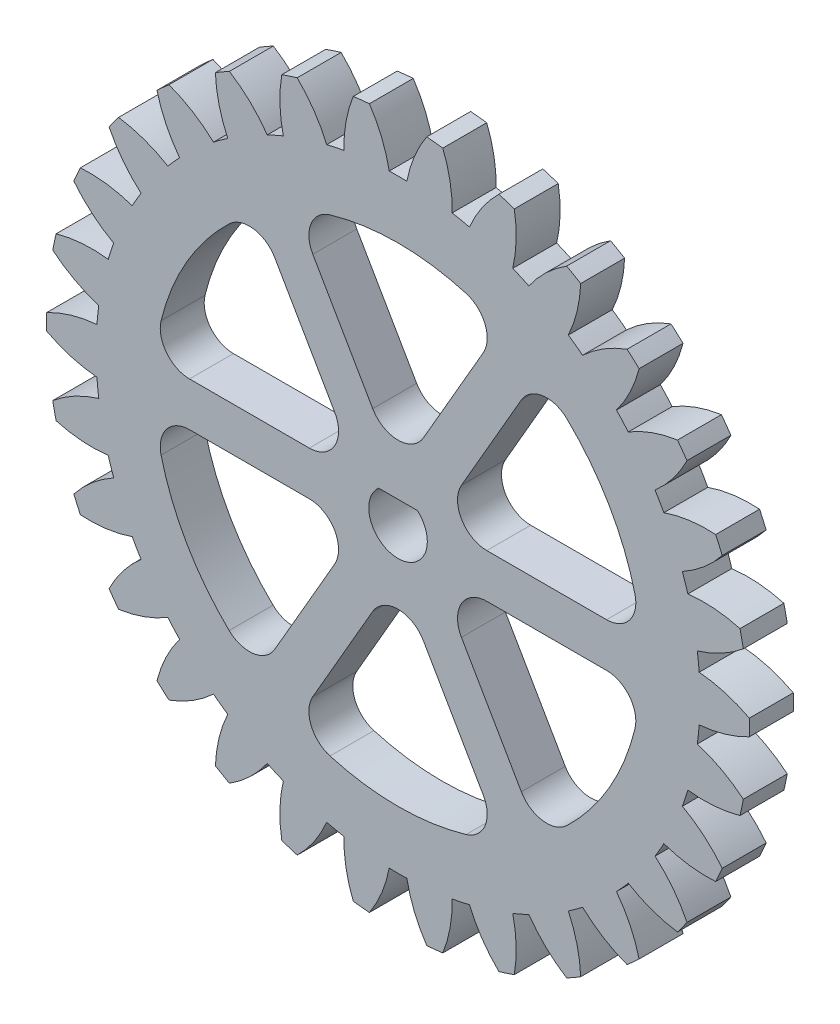
SolidWorks part; units mm, degrees
ref_plane "Front Plane" through (0, 0, 0) normal (0, 0, 1) x (1, 0, 0)
ref_plane "Top Plane" through (0, 0, 0) normal (0, 1, 0) x (1, 0, 0)
ref_plane "Right Plane" through (0, 0, 0) normal (1, 0, 0) x (0, 0, -1)
sketch "Sketch1" plane through (0, 0, 0) normal (0, 0, 1) x (1, 0, 0)
  circle A1 centre (0, 0) radius 24
  dimension "addendumDiameter" = 48
extrude "Boss-Extrude1" add sketch "Sketch1" along normal blind 3
sketch "Sketch2" plane through (0, 0, 3) normal (0, 0, 1) x (1, 0, 0)
  line L0 (0, 0) -> (0, 31) construction
  line L1 (0, 0) -> (-2.7303, 25.9775) construction
  line L2 (-1.1705, 22.4695) -> (-2.3486, 22.3457) construction
  circle A0 centre (0, 0) radius 21.1431 construction
  circle A1 centre (0, 0) radius 22.5 construction
  circle A2 centre (0, 0) radius 20.625 construction
  arc A5 (1.9581, 23.92) -> (0.6019, 20.6162) centre (9.4404, 18.9185) ccw
  arc A8 (1.9581, 23.92) -> (-1.9581, 23.92) centre (0, 0) ccw
  circle A9 centre (0, 0) radius 24 construction
  arc A10 (0.6019, 20.6162) -> (-0.6019, 20.6162) centre (0, 0) ccw
  circle A11 centre (0, 0) radius 24 construction
  arc A12 (-1.9581, 23.92) -> (-0.6019, 20.6162) centre (-9.4404, 18.9185) cw
  dimension "Dedendum Circle" = 41.25
  dimension "Base Diameter" = 42.2862
  dimension "D7" = 45
  dimension "D4" = 9
  dimension "D1" = 9
  dimension "D3" = 6
  dimension "D2" = 1.1781
extrude "Cut-Extrude1" cut sketch "Sketch2" against normal blind 3
pattern_circular "CirPattern1" count 30 over 360 about axis through (0, 0, 3) along (0, 0, 1) of "Cut-Extrude1"
sketch "Sketch3" plane through (0, 0, 3) normal (0, 0, 1) x (1, 0, 0)
  line L0 (0, 0) -> (0, 26.8242) construction
  line L1 (-9.6877, 3) -> (9.6877, 3) construction
  line L2 (0, 3) -> (7, 15.1244)
  line L4 (-7, 15.1244) -> (0, 3)
  arc A0 (-7, 15.1244) -> (7, 15.1244) centre (0, 0) cw
  arc A3 (4.8751, 20.0406) -> (3.6976, 20.2909) centre (0, 0) ccw construction
  dimension "D1" = 3
  dimension "D4" = 14
extrude "Cut-Extrude2" cut sketch "Sketch3" against normal through all
fillet "Fillet2" radius 2 3 edges at (-7, 15.1244, 1.5) (0, 3, 1.5) (7, 15.1244, 1.5)
ref_axis "Axis1" through (0, 0, 0) along (0, 0, 1)
pattern_circular "CirPattern3" count 6 over 360 about axis through (0, 0, 0) along (0, 0, 1) of "Cut-Extrude2", "Fillet2"
sketch "Sketch4" plane through (0, 0, 3) normal (0, 0, 1) x (1, 0, 0)
  line L0 (-1.3229, 1.5) -> (1.3229, 1.5)
  arc A0 (-1.3229, 1.5) -> (1.3229, 1.5) centre (0, 0) ccw
  dimension "D2" = 4
  dimension "D1" = 1.5
extrude "Cut-Extrude3" cut sketch "Sketch4" against normal through all
equation "\"module\"= 1.5"
equation "\"teeth\"= 30"
equation "\"pressureAngle\"= 20deg"
equation "\"gearThickness\"= 3"
equation "\"addendumFactor\"= 1"
equation "\"dedendumFactor\"= 1.25"
equation "\"pitch\"= 1 / \"module\""
equation "\"pitchDiameter\"= \"teeth\" / \"pitch\""
equation "\"addendum\"= \"addendumFactor\" / \"pitch\""
equation "\"dedendum\"= \"dedendumFactor\" / \"pitch\""
equation "\"D1@Boss-Extrude1\"=\"gearThickness\""
equation "\"D3@Sketch2\"=180/\"teeth\""
equation "\"addendumDiameter@Sketch1\"=\"pitchDiameter\" + 2 * \"addendum\""
equation "\"Dedendum Circle@Sketch2\" = \"pitchDiameter\" - 2 * \"dedendum\""
equation "\"Base Diameter@Sketch2\" = \"pitchDiameter\" * cos ( \"pressureAngle\" ) "
equation "\"D7@Sketch2\"= \"pitchDiameter\""
equation "\"D4@Sketch2\"= \"pitchDiameter\" / 5"
equation "\"D1@Sketch2\"= \"pitchDiameter\" / 5"
equation "\"D2@Sketch2\"= PI / 2 / \"pitch\" / 2"
equation "\"D1@CirPattern1\"= \"teeth\""
